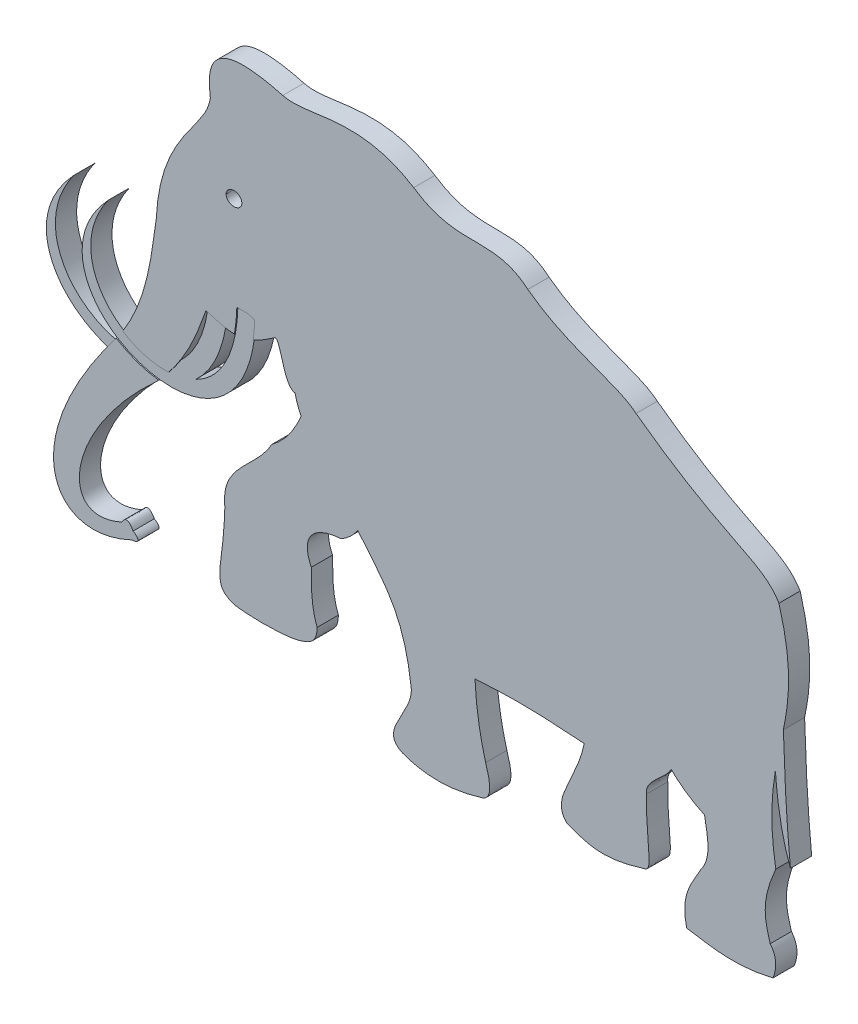
SolidWorks part; units mm, degrees
ref_plane "Plan de face" through (0, 0, 0) normal (0, 0, 1) x (1, 0, 0)
ref_plane "Plan de dessus" through (0, 0, 0) normal (0, 1, 0) x (1, 0, 0)
ref_plane "Plan de droite" through (0, 0, 0) normal (1, 0, 0) x (0, 0, -1)
sketch "Model" plane through (0, 0, 0) normal (0, 0, 1) x (1, 0, 0)
  line L0 (248.1084, -239.3251) -> (301.9242, -314.2399)
  line L1 (686.5238, -260.843) -> (694.4103, -257.2566)
  spline S0 degree 3 poles (301.9242, -314.2399) (295.2295, -323.0056) (293.23, -331.7727) (278.7279, -340.5398) knots 0 0 0 0 1 1 1 1
  spline S1 degree 3 poles (278.7279, -340.5398) (254.5292, -342.3381) (239.2631, -354.1813) (250.429, -377.9962) knots 1 1 1 1 2 2 2 2
  spline S2 degree 3 poles (250.429, -377.9962) (250.7714, -393.4048) (249.7741, -408.8129) (255.9949, -424.2201) knots 2 2 2 2 3 3 3 3
  spline S3 degree 3 poles (255.9949, -424.2201) (255.639, -432.7619) (253.4598, -438.1342) (245.3247, -440.9567) knots 3 3 3 3 4 4 4 4
  spline S4 degree 3 poles (245.3247, -440.9567) (232.7989, -448.2596) (189.6535, -447.0308) (178.5197, -444.941) knots 4 4 4 4 5 5 5 5
  spline S5 degree 3 poles (178.5197, -444.941) (161.3948, -439.7392) (164.8538, -429.6816) (164.602, -419.4387) knots 5 5 5 5 6 6 6 6
  spline S6 degree 3 poles (164.602, -419.4387) (166.1483, -404.8297) (169.703, -383.7044) (168.7761, -361.6592) knots 6 6 6 6 7 7 7 7
  spline S7 degree 3 poles (168.7761, -361.6592) (169.3183, -333.355) (200.344, -320.6405) (212.8499, -296.7061) knots 7 7 7 7 8 8 8 8
  spline S8 degree 3 poles (212.8499, -296.7061) (232.5185, -282.1109) (240.8466, -262.3516) (248.1084, -239.3251) knots 8 8 8 8 9 9 9 9
  spline S9 degree 3 poles (25.6291, -171.1053) (-78.331, -281.7881) (164.8394, -380.2969) (171.1134, -200.6289) knots 2 2 2 2 3 3 3 3
  spline S10 degree 3 poles (153.5278, -198.3402) (149.0453, -356.6449) (-50.4862, -276.4662) (25.6291, -171.1053) knots 1 1 1 1 2 2 2 2
  spline S11 degree 3 poles (171.1134, -200.6289) (165.7403, -197.3457) (159.5823, -198.1088) (153.5278, -198.3402) knots 0 0 0 0 1 1 1 1
  spline S12 degree 3 poles (694.4103, -257.2566) (695.4208, -304.563) (697.1437, -351.666) (701.8335, -397.9202) knots 0 0 0 0 1 1 1 1
  spline S13 degree 3 poles (701.8335, -397.9202) (687.3431, -360.1465) (685.441, -308.9069) (686.5238, -260.843) knots 1 1 1 1 2 2 2 2
  spline S14 degree 3 poles (682.8079, -468.9333) (688.369, -475.8083) (689.7625, -484.4731) (685.4324, -495.5966) knots 31 31 31 31 32 32 32 32
  spline S15 degree 3 poles (688.0569, -405.4295) (674.1573, -436.5487) (677.1662, -450.4028) (682.8079, -468.9333) knots 30 30 30 30 31 31 31 31
  spline S16 degree 3 poles (691.0004, -187.0392) (719.3676, -283.9641) (670.9806, -305.2568) (688.0569, -405.4295) knots 29 29 29 29 30 30 30 30
  spline S17 degree 3 poles (556.3877, -99.5257) (642.7673, -162.7708) (674.5552, -159.525) (691.0004, -187.0392) knots 28 28 28 28 29 29 29 29
  spline S18 degree 3 poles (454.4856, -49.2743) (493.3074, -78.3308) (537.7653, -83.4723) (556.3877, -99.5257) knots 27 27 27 27 28 28 28 28
  spline S19 degree 3 poles (346.8861, -19.9704) (389.7375, -49.2339) (421.2332, -21.029) (454.4856, -49.2743) knots 26 26 26 26 27 27 27 27
  spline S20 degree 3 poles (223.5405, -6.4456) (248.6374, -12.988) (294.1249, 13.0793) (346.8861, -19.9704) knots 25 25 25 25 26 26 26 26
  spline S21 degree 3 poles (155.3066, -42.512) (150.0494, -7.9268) (163.8615, 9.5951) (223.5405, -6.4456) knots 24 24 24 24 25 25 25 25
  spline S22 degree 3 poles (104.3556, -166.7051) (108.0056, -90.8591) (151.5201, -71.6657) (155.3066, -42.512) knots 23 23 23 23 24 24 24 24
  spline S23 degree 3 poles (64.429, -285.9688) (97.7651, -242.8014) (99.6894, -195.1846) (104.3556, -166.7051) knots 22 22 22 22 23 23 23 23
  spline S24 degree 3 poles (81.2583, -440.227) (11.0648, -474.2336) (-33.8922, -415.6463) (64.429, -285.9688) knots 21 21 21 21 22 22 22 22
  spline S25 degree 3 poles (82.536, -432.3929) (85.8168, -434.031) (91.6451, -439.7382) (81.2583, -440.227) knots 20 20 20 20 21 21 21 21
  spline S26 degree 3 poles (72.0705, -430.2411) (76.0632, -422.4504) (80.7158, -428.6315) (82.536, -432.3929) knots 19 19 19 19 20 20 20 20
  spline S27 degree 3 poles (105.1497, -298.7683) (14.8816, -380.7089) (13.2057, -457.0612) (72.0705, -430.2411) knots 18 18 18 18 19 19 19 19
  spline S28 degree 3 poles (151.2097, -218.1993) (141.3571, -245.6541) (131.9728, -269.5625) (105.1497, -298.7683) knots 17 17 17 17 18 18 18 18
  spline S29 degree 3 poles (215.6607, -208.1153) (182.5696, -231.755) (171.7983, -223.2184) (151.2097, -218.1993) knots 16 16 16 16 17 17 17 17
  spline S30 degree 3 poles (235.1243, -243.405) (223.5218, -242.3888) (221.7119, -203.7932) (215.6607, -208.1153) knots 15 15 15 15 16 16 16 16
  spline S31 degree 3 poles (302.2716, -335.5513) (284.6381, -313.5233) (242.1377, -277.4728) (235.1243, -243.405) knots 14 14 14 14 15 15 15 15
  spline S32 degree 3 poles (344.4077, -428.0965) (337.8376, -374.1108) (319.875, -358.4822) (302.2716, -335.5513) knots 13 13 13 13 14 14 14 14
  spline S33 degree 3 poles (336.3884, -486.5801) (312.2133, -475.3205) (347.7843, -450.1141) (344.4077, -428.0965) knots 12 12 12 12 13 13 13 13
  spline S34 degree 3 poles (411.0902, -485.6468) (383.7985, -494.1735) (358.7337, -495.0502) (336.3884, -486.5801) knots 11 11 11 11 12 12 12 12
  spline S35 degree 3 poles (414.6968, -455.1905) (416.9182, -462.6339) (423.6596, -482.1542) (411.0902, -485.6468) knots 10 10 10 10 11 11 11 11
  spline S36 degree 3 poles (404.6223, -391.9048) (405.8026, -415.5826) (409.0097, -434.3886) (414.6968, -455.1905) knots 9 9 9 9 10 10 10 10
  spline S37 degree 3 poles (507.5976, -393.2142) (474.8275, -391.2485) (454.1935, -388.7491) (404.6223, -391.9048) knots 8 8 8 8 9 9 9 9
  spline S38 degree 3 poles (491.2286, -466.2926) (475.3057, -451.0646) (500.5186, -427.7775) (507.5976, -393.2142) knots 7 7 7 7 8 8 8 8
  spline S39 degree 3 poles (563.9287, -467.0888) (526.7358, -478.7256) (512.5024, -474.8272) (491.2286, -466.2926) knots 6 6 6 6 7 7 7 7
  spline S40 degree 3 poles (566.2676, -405.0037) (565.0839, -441.931) (573.8871, -466.4112) (563.9287, -467.0888) knots 5 5 5 5 6 6 6 6
  spline S41 degree 3 poles (589.7814, -373.1996) (581.9955, -386.1446) (564.8589, -392.8883) (566.2676, -405.0037) knots 4 4 4 4 5 5 5 5
  spline S42 degree 3 poles (620.9092, -394.8197) (613.1905, -391.6305) (596.3109, -381.2932) (589.7814, -373.1996) knots 3 3 3 3 4 4 4 4
  spline S43 degree 3 poles (617.1985, -441.4959) (628.4719, -426.468) (623.235, -409.8472) (620.9092, -394.8197) knots 2 2 2 2 3 3 3 3
  spline S44 degree 3 poles (604.0768, -495.5966) (597.9194, -468.5168) (609.2765, -456.4831) (617.1985, -441.4959) knots 1 1 1 1 2 2 2 2
  spline S45 degree 3 poles (685.4324, -495.5966) (647.9339, -504.5132) (627.4122, -498.8457) (604.0768, -495.5966) knots 0 0 0 0 1 1 1 1
  spline S46 degree 3 poles (590.6978, -374.1904) (539.7869, -400.8334) (527.9161, -394.1892) (506.1403, -393.1667) knots 1 1 1 1 2 2 2 2
  spline S47 degree 3 poles (549.6633, -223.3853) (544.7302, -281.4936) (550.1197, -334.0427) (590.6978, -374.1904) knots 0 0 0 0 1 1 1 1
  spline S48 degree 3 poles (426.2572, -340.9377) (425.0145, -313.7827) (425.3804, -284.5528) (414.66, -269.6101) knots 1 1 1 1 2 2 2 2
  spline S49 degree 3 poles (404.9179, -391.9423) (405.9508, -371.4602) (421.8867, -360.439) (426.2572, -340.9377) knots 0 0 0 0 1 1 1 1
  spline S50 degree 3 poles (269.9127, -224.1827) (248.4308, -210.3968) (243.355, -183.4512) (227.2309, -166.801) knots 4 4 4 4 5 5 5 5
  spline S51 degree 3 poles (351.1024, -119.382) (294.0392, -147.0682) (290.6761, -187.727) (269.9127, -224.1827) knots 3 3 3 3 4 4 4 4
  spline S52 degree 3 poles (368.2673, -91.4885) (362.545, -102.9) (356.8227, -118.7907) (351.1024, -119.382) knots 2 2 2 2 3 3 3 3
  spline S53 degree 3 poles (334.864, -58.0152) (368.9673, -57.1161) (357.1369, -80.3288) (368.2673, -91.4885) knots 1 1 1 1 2 2 2 2
  spline S54 degree 3 poles (229.5515, -48.8509) (256.9822, -39.8213) (270.9943, -60.5377) (334.864, -58.0152) knots 0 0 0 0 1 1 1 1
  spline S55 degree 3 poles (185.0142, -113.6037) (185.0142, -109.9723) (181.6895, -107.029) (177.5912, -107.029) (173.4909, -107.029) (170.1679, -109.9723) (170.1679, -113.6037) knots 2 2 2 2 3 3 3 4 4 4 4
  spline S56 degree 3 poles (170.1679, -113.6037) (170.1679, -117.2352) (173.4909, -120.1785) (177.5912, -120.1785) (181.6895, -120.1785) (185.0142, -117.2352) (185.0142, -113.6037) knots 0 0 0 0 1 1 1 2 2 2 2
  spline S57 degree 3 poles (58.1685, -175.0475) (-41.0917, -280.725) (191.0848, -374.7819) (197.0769, -203.2358) knots 2 2 2 2 3 3 3 3
  spline S58 degree 3 poles (180.286, -201.0508) (176.0068, -352.1983) (-14.5056, -275.6445) (58.1685, -175.0475) knots 1 1 1 1 2 2 2 2
  spline S59 degree 3 poles (197.0769, -203.2358) (191.9463, -200.101) (186.0669, -200.8293) (180.286, -201.0508) knots 0 0 0 0 1 1 1 1
extrude "Boss.-Extru.1" add sketch "Model" along normal blind 20 contours S59 S57 S29 S30 S31 S8 L0 S0 S32 S33 S34 S35 S36 S37 S38 S46 S41 S42 S47 S43 S44 S45 S14 S15 S16 S13 L1 S12 S17 S18 S19 S20 S21 S22 S23 S58 S10 S28 | S0 S31 S8 S7 S6 S5 S4 S3 S2 S1 | S41 S46 S38 S39 S40 | S28 S9 S24 S25 S26 S27 | S57 S10 S23 S24 S9 S28 | S57 S23 S10 | S58 S28 S10 | S29 S9 S11 S10 | S13 L1 S12 | L0 S0 S1 S2 S3 S4 S5 S6 S7 S8 region at (415.0252, -224.2077, 0) region at (219.9742, -365.8319, 0) region at (161.7862, -209.6887, 0) region at (44.5341, -370.9669, 0) region at (77.4933, -294.0595, 0) region at (114.7872, -281.6253, 0) region at (68.3589, -285.0647, 0) region at (531.9975, -433.1095, 0)
sketch "Esquisse3" plane through (0, 0, 0) normal (0, 0, 1) x (1, 0, 0)
  line L0 (248.1084, -239.3251) -> (301.9242, -314.2399)
  line L1 (686.5238, -260.843) -> (694.4103, -257.2566)
  spline S0 degree 3 poles (301.9242, -314.2399) (295.2295, -323.0056) (293.23, -331.7727) (278.7279, -340.5398) knots 0 0 0 0 1 1 1 1
  spline S1 degree 3 poles (278.7279, -340.5398) (254.5292, -342.3381) (239.2631, -354.1813) (250.429, -377.9962) knots 1 1 1 1 2 2 2 2
  spline S2 degree 3 poles (250.429, -377.9962) (250.7714, -393.4048) (249.7741, -408.8129) (255.9949, -424.2201) knots 2 2 2 2 3 3 3 3
  spline S3 degree 3 poles (255.9949, -424.2201) (255.639, -432.7619) (253.4598, -438.1342) (245.3247, -440.9567) knots 3 3 3 3 4 4 4 4
  spline S4 degree 3 poles (245.3247, -440.9567) (232.7989, -448.2596) (189.6535, -447.0308) (178.5197, -444.941) knots 4 4 4 4 5 5 5 5
  spline S5 degree 3 poles (178.5197, -444.941) (161.3948, -439.7392) (164.8538, -429.6816) (164.602, -419.4387) knots 5 5 5 5 6 6 6 6
  spline S6 degree 3 poles (164.602, -419.4387) (166.1483, -404.8297) (169.703, -383.7044) (168.7761, -361.6592) knots 6 6 6 6 7 7 7 7
  spline S7 degree 3 poles (168.7761, -361.6592) (169.3183, -333.355) (200.344, -320.6405) (212.8499, -296.7061) knots 7 7 7 7 8 8 8 8
  spline S8 degree 3 poles (212.8499, -296.7061) (232.5185, -282.1109) (240.8466, -262.3516) (248.1084, -239.3251) knots 8 8 8 8 9 9 9 9
  spline S9 degree 3 poles (25.6291, -171.1053) (-78.331, -281.7881) (164.8394, -380.2969) (171.1134, -200.6289) knots 2 2 2 2 3 3 3 3
  spline S10 degree 3 poles (153.5278, -198.3402) (149.0453, -356.6449) (-50.4862, -276.4662) (25.6291, -171.1053) knots 1 1 1 1 2 2 2 2
  spline S11 degree 3 poles (171.1134, -200.6289) (165.7403, -197.3457) (159.5823, -198.1088) (153.5278, -198.3402) knots 0 0 0 0 1 1 1 1
  spline S12 degree 3 poles (694.4103, -257.2566) (695.4208, -304.563) (697.1437, -351.666) (701.8335, -397.9202) knots 0 0 0 0 1 1 1 1
  spline S13 degree 3 poles (701.8335, -397.9202) (687.3431, -360.1465) (685.441, -308.9069) (686.5238, -260.843) knots 1 1 1 1 2 2 2 2
  spline S14 degree 3 poles (682.8079, -468.9333) (688.369, -475.8083) (689.7625, -484.4731) (685.4324, -495.5966) knots 31 31 31 31 32 32 32 32
  spline S15 degree 3 poles (688.0569, -405.4295) (674.1573, -436.5487) (677.1662, -450.4028) (682.8079, -468.9333) knots 30 30 30 30 31 31 31 31
  spline S16 degree 3 poles (691.0004, -187.0392) (719.3676, -283.9641) (670.9806, -305.2568) (688.0569, -405.4295) knots 29 29 29 29 30 30 30 30
  spline S17 degree 3 poles (556.3877, -99.5257) (642.7673, -162.7708) (674.5552, -159.525) (691.0004, -187.0392) knots 28 28 28 28 29 29 29 29
  spline S18 degree 3 poles (454.4856, -49.2743) (493.3074, -78.3308) (537.7653, -83.4723) (556.3877, -99.5257) knots 27 27 27 27 28 28 28 28
  spline S19 degree 3 poles (346.8861, -19.9704) (389.7375, -49.2339) (421.2332, -21.029) (454.4856, -49.2743) knots 26 26 26 26 27 27 27 27
  spline S20 degree 3 poles (223.5405, -6.4456) (248.6374, -12.988) (294.1249, 13.0793) (346.8861, -19.9704) knots 25 25 25 25 26 26 26 26
  spline S21 degree 3 poles (155.3066, -42.512) (150.0494, -7.9268) (163.8615, 9.5951) (223.5405, -6.4456) knots 24 24 24 24 25 25 25 25
  spline S22 degree 3 poles (104.3556, -166.7051) (108.0056, -90.8591) (151.5201, -71.6657) (155.3066, -42.512) knots 23 23 23 23 24 24 24 24
  spline S23 degree 3 poles (64.429, -285.9688) (97.7651, -242.8014) (99.6894, -195.1846) (104.3556, -166.7051) knots 22 22 22 22 23 23 23 23
  spline S24 degree 3 poles (81.2583, -440.227) (11.0648, -474.2336) (-33.8922, -415.6463) (64.429, -285.9688) knots 21 21 21 21 22 22 22 22
  spline S25 degree 3 poles (82.536, -432.3929) (85.8168, -434.031) (91.6451, -439.7382) (81.2583, -440.227) knots 20 20 20 20 21 21 21 21
  spline S26 degree 3 poles (72.0705, -430.2411) (76.0632, -422.4504) (80.7158, -428.6315) (82.536, -432.3929) knots 19 19 19 19 20 20 20 20
  spline S27 degree 3 poles (105.1497, -298.7683) (14.8816, -380.7089) (13.2057, -457.0612) (72.0705, -430.2411) knots 18 18 18 18 19 19 19 19
  spline S28 degree 3 poles (151.2097, -218.1993) (141.3571, -245.6541) (131.9728, -269.5625) (105.1497, -298.7683) knots 17 17 17 17 18 18 18 18
  spline S29 degree 3 poles (215.6607, -208.1153) (182.5696, -231.755) (171.7983, -223.2184) (151.2097, -218.1993) knots 16 16 16 16 17 17 17 17
  spline S30 degree 3 poles (235.1243, -243.405) (223.5218, -242.3888) (221.7119, -203.7932) (215.6607, -208.1153) knots 15 15 15 15 16 16 16 16
  spline S31 degree 3 poles (302.2716, -335.5513) (284.6381, -313.5233) (242.1377, -277.4728) (235.1243, -243.405) knots 14 14 14 14 15 15 15 15
  spline S32 degree 3 poles (344.4077, -428.0965) (337.8376, -374.1108) (319.875, -358.4822) (302.2716, -335.5513) knots 13 13 13 13 14 14 14 14
  spline S33 degree 3 poles (336.3884, -486.5801) (312.2133, -475.3205) (347.7843, -450.1141) (344.4077, -428.0965) knots 12 12 12 12 13 13 13 13
  spline S34 degree 3 poles (411.0902, -485.6468) (383.7985, -494.1735) (358.7337, -495.0502) (336.3884, -486.5801) knots 11 11 11 11 12 12 12 12
  spline S35 degree 3 poles (414.6968, -455.1905) (416.9182, -462.6339) (423.6596, -482.1542) (411.0902, -485.6468) knots 10 10 10 10 11 11 11 11
  spline S36 degree 3 poles (404.6223, -391.9048) (405.8026, -415.5826) (409.0097, -434.3886) (414.6968, -455.1905) knots 9 9 9 9 10 10 10 10
  spline S37 degree 3 poles (507.5976, -393.2142) (474.8275, -391.2485) (454.1935, -388.7491) (404.6223, -391.9048) knots 8 8 8 8 9 9 9 9
  spline S38 degree 3 poles (491.2286, -466.2926) (475.3057, -451.0646) (500.5186, -427.7775) (507.5976, -393.2142) knots 7 7 7 7 8 8 8 8
  spline S39 degree 3 poles (563.9287, -467.0888) (526.7358, -478.7256) (512.5024, -474.8272) (491.2286, -466.2926) knots 6 6 6 6 7 7 7 7
  spline S40 degree 3 poles (566.2676, -405.0037) (565.0839, -441.931) (573.8871, -466.4112) (563.9287, -467.0888) knots 5 5 5 5 6 6 6 6
  spline S41 degree 3 poles (589.7814, -373.1996) (581.9955, -386.1446) (564.8589, -392.8883) (566.2676, -405.0037) knots 4 4 4 4 5 5 5 5
  spline S42 degree 3 poles (620.9092, -394.8197) (613.1905, -391.6305) (596.3109, -381.2932) (589.7814, -373.1996) knots 3 3 3 3 4 4 4 4
  spline S43 degree 3 poles (617.1985, -441.4959) (628.4719, -426.468) (623.235, -409.8472) (620.9092, -394.8197) knots 2 2 2 2 3 3 3 3
  spline S44 degree 3 poles (604.0768, -495.5966) (597.9194, -468.5168) (609.2765, -456.4831) (617.1985, -441.4959) knots 1 1 1 1 2 2 2 2
  spline S45 degree 3 poles (685.4324, -495.5966) (647.9339, -504.5132) (627.4122, -498.8457) (604.0768, -495.5966) knots 0 0 0 0 1 1 1 1
  spline S46 degree 3 poles (590.6978, -374.1904) (539.7869, -400.8334) (527.9161, -394.1892) (506.1403, -393.1667) knots 1 1 1 1 2 2 2 2
  spline S47 degree 3 poles (549.6633, -223.3853) (544.7302, -281.4936) (550.1197, -334.0427) (590.6978, -374.1904) knots 0 0 0 0 1 1 1 1
  spline S48 degree 3 poles (426.2572, -340.9377) (425.0145, -313.7827) (425.3804, -284.5528) (414.66, -269.6101) knots 1 1 1 1 2 2 2 2
  spline S49 degree 3 poles (404.9179, -391.9423) (405.9508, -371.4602) (421.8867, -360.439) (426.2572, -340.9377) knots 0 0 0 0 1 1 1 1
  spline S50 degree 3 poles (269.9127, -224.1827) (248.4308, -210.3968) (243.355, -183.4512) (227.2309, -166.801) knots 4 4 4 4 5 5 5 5
  spline S51 degree 3 poles (351.1024, -119.382) (294.0392, -147.0682) (290.6761, -187.727) (269.9127, -224.1827) knots 3 3 3 3 4 4 4 4
  spline S52 degree 3 poles (368.2673, -91.4885) (362.545, -102.9) (356.8227, -118.7907) (351.1024, -119.382) knots 2 2 2 2 3 3 3 3
  spline S53 degree 3 poles (334.864, -58.0152) (368.9673, -57.1161) (357.1369, -80.3288) (368.2673, -91.4885) knots 1 1 1 1 2 2 2 2
  spline S54 degree 3 poles (229.5515, -48.8509) (256.9822, -39.8213) (270.9943, -60.5377) (334.864, -58.0152) knots 0 0 0 0 1 1 1 1
  spline S55 degree 3 poles (185.0142, -113.6037) (185.0142, -109.9723) (181.6895, -107.029) (177.5912, -107.029) (173.4909, -107.029) (170.1679, -109.9723) (170.1679, -113.6037) knots 2 2 2 2 3 3 3 4 4 4 4
  spline S56 degree 3 poles (170.1679, -113.6037) (170.1679, -117.2352) (173.4909, -120.1785) (177.5912, -120.1785) (181.6895, -120.1785) (185.0142, -117.2352) (185.0142, -113.6037) knots 0 0 0 0 1 1 1 2 2 2 2
  spline S57 degree 3 poles (58.1685, -175.0475) (-41.0917, -280.725) (191.0848, -374.7819) (197.0769, -203.2358) knots 2 2 2 2 3 3 3 3
  spline S58 degree 3 poles (180.286, -201.0508) (176.0068, -352.1983) (-14.5056, -275.6445) (58.1685, -175.0475) knots 1 1 1 1 2 2 2 2
  spline S59 degree 3 poles (197.0769, -203.2358) (191.9463, -200.101) (186.0669, -200.8293) (180.286, -201.0508) knots 0 0 0 0 1 1 1 1
extrude "Boss.-Extru.2" add sketch "Esquisse3" along normal blind 19 contours S29 S58 S9 S57 | S58 S9 S29 S10 S28 | S57 S59 S58 S29 | S28 S58 S10 S57 | S9 S58 S28 S57 | S58 S57 S59 | S9 S11 S10 region at (165.0031, -263.0982, 0) region at (187.5826, -211.9729, 0) region at (121.2048, -289.3126, 0) region at (147.2657, -253.5134, 0) region at (98.2499, -290.4263, 0)
sketch "Esquisse6" plane through (0, 0, 0) normal (0, 0, 1) x (1, 0, 0)
  line L0 (248.1084, -239.3251) -> (301.9242, -314.2399)
  line L1 (686.5238, -260.843) -> (694.4103, -257.2566)
  spline S0 degree 3 poles (301.9242, -314.2399) (295.2295, -323.0056) (293.23, -331.7727) (278.7279, -340.5398) knots 0 0 0 0 1 1 1 1
  spline S1 degree 3 poles (278.7279, -340.5398) (254.5292, -342.3381) (239.2631, -354.1813) (250.429, -377.9962) knots 1 1 1 1 2 2 2 2
  spline S2 degree 3 poles (250.429, -377.9962) (250.7714, -393.4048) (249.7741, -408.8129) (255.9949, -424.2201) knots 2 2 2 2 3 3 3 3
  spline S3 degree 3 poles (255.9949, -424.2201) (255.639, -432.7619) (253.4598, -438.1342) (245.3247, -440.9567) knots 3 3 3 3 4 4 4 4
  spline S4 degree 3 poles (245.3247, -440.9567) (232.7989, -448.2596) (189.6535, -447.0308) (178.5197, -444.941) knots 4 4 4 4 5 5 5 5
  spline S5 degree 3 poles (178.5197, -444.941) (161.3948, -439.7392) (164.8538, -429.6816) (164.602, -419.4387) knots 5 5 5 5 6 6 6 6
  spline S6 degree 3 poles (164.602, -419.4387) (166.1483, -404.8297) (169.703, -383.7044) (168.7761, -361.6592) knots 6 6 6 6 7 7 7 7
  spline S7 degree 3 poles (168.7761, -361.6592) (169.3183, -333.355) (200.344, -320.6405) (212.8499, -296.7061) knots 7 7 7 7 8 8 8 8
  spline S8 degree 3 poles (212.8499, -296.7061) (232.5185, -282.1109) (240.8466, -262.3516) (248.1084, -239.3251) knots 8 8 8 8 9 9 9 9
  spline S9 degree 3 poles (25.6291, -171.1053) (-78.331, -281.7881) (164.8394, -380.2969) (171.1134, -200.6289) knots 2 2 2 2 3 3 3 3
  spline S10 degree 3 poles (153.5278, -198.3402) (149.0453, -356.6449) (-50.4862, -276.4662) (25.6291, -171.1053) knots 1 1 1 1 2 2 2 2
  spline S11 degree 3 poles (171.1134, -200.6289) (165.7403, -197.3457) (159.5823, -198.1088) (153.5278, -198.3402) knots 0 0 0 0 1 1 1 1
  spline S12 degree 3 poles (694.4103, -257.2566) (695.4208, -304.563) (697.1437, -351.666) (701.8335, -397.9202) knots 0 0 0 0 1 1 1 1
  spline S13 degree 3 poles (701.8335, -397.9202) (687.3431, -360.1465) (685.441, -308.9069) (686.5238, -260.843) knots 1 1 1 1 2 2 2 2
  spline S14 degree 3 poles (682.8079, -468.9333) (688.369, -475.8083) (689.7625, -484.4731) (685.4324, -495.5966) knots 31 31 31 31 32 32 32 32
  spline S15 degree 3 poles (688.0569, -405.4295) (674.1573, -436.5487) (677.1662, -450.4028) (682.8079, -468.9333) knots 30 30 30 30 31 31 31 31
  spline S16 degree 3 poles (691.0004, -187.0392) (719.3676, -283.9641) (670.9806, -305.2568) (688.0569, -405.4295) knots 29 29 29 29 30 30 30 30
  spline S17 degree 3 poles (556.3877, -99.5257) (642.7673, -162.7708) (674.5552, -159.525) (691.0004, -187.0392) knots 28 28 28 28 29 29 29 29
  spline S18 degree 3 poles (454.4856, -49.2743) (493.3074, -78.3308) (537.7653, -83.4723) (556.3877, -99.5257) knots 27 27 27 27 28 28 28 28
  spline S19 degree 3 poles (346.8861, -19.9704) (389.7375, -49.2339) (421.2332, -21.029) (454.4856, -49.2743) knots 26 26 26 26 27 27 27 27
  spline S20 degree 3 poles (223.5405, -6.4456) (248.6374, -12.988) (294.1249, 13.0793) (346.8861, -19.9704) knots 25 25 25 25 26 26 26 26
  spline S21 degree 3 poles (155.3066, -42.512) (150.0494, -7.9268) (163.8615, 9.5951) (223.5405, -6.4456) knots 24 24 24 24 25 25 25 25
  spline S22 degree 3 poles (104.3556, -166.7051) (108.0056, -90.8591) (151.5201, -71.6657) (155.3066, -42.512) knots 23 23 23 23 24 24 24 24
  spline S23 degree 3 poles (64.429, -285.9688) (97.7651, -242.8014) (99.6894, -195.1846) (104.3556, -166.7051) knots 22 22 22 22 23 23 23 23
  spline S24 degree 3 poles (81.2583, -440.227) (11.0648, -474.2336) (-33.8922, -415.6463) (64.429, -285.9688) knots 21 21 21 21 22 22 22 22
  spline S25 degree 3 poles (82.536, -432.3929) (85.8168, -434.031) (91.6451, -439.7382) (81.2583, -440.227) knots 20 20 20 20 21 21 21 21
  spline S26 degree 3 poles (72.0705, -430.2411) (76.0632, -422.4504) (80.7158, -428.6315) (82.536, -432.3929) knots 19 19 19 19 20 20 20 20
  spline S27 degree 3 poles (105.1497, -298.7683) (14.8816, -380.7089) (13.2057, -457.0612) (72.0705, -430.2411) knots 18 18 18 18 19 19 19 19
  spline S28 degree 3 poles (151.2097, -218.1993) (141.3571, -245.6541) (131.9728, -269.5625) (105.1497, -298.7683) knots 17 17 17 17 18 18 18 18
  spline S29 degree 3 poles (215.6607, -208.1153) (182.5696, -231.755) (171.7983, -223.2184) (151.2097, -218.1993) knots 16 16 16 16 17 17 17 17
  spline S30 degree 3 poles (235.1243, -243.405) (223.5218, -242.3888) (221.7119, -203.7932) (215.6607, -208.1153) knots 15 15 15 15 16 16 16 16
  spline S31 degree 3 poles (302.2716, -335.5513) (284.6381, -313.5233) (242.1377, -277.4728) (235.1243, -243.405) knots 14 14 14 14 15 15 15 15
  spline S32 degree 3 poles (344.4077, -428.0965) (337.8376, -374.1108) (319.875, -358.4822) (302.2716, -335.5513) knots 13 13 13 13 14 14 14 14
  spline S33 degree 3 poles (336.3884, -486.5801) (312.2133, -475.3205) (347.7843, -450.1141) (344.4077, -428.0965) knots 12 12 12 12 13 13 13 13
  spline S34 degree 3 poles (411.0902, -485.6468) (383.7985, -494.1735) (358.7337, -495.0502) (336.3884, -486.5801) knots 11 11 11 11 12 12 12 12
  spline S35 degree 3 poles (414.6968, -455.1905) (416.9182, -462.6339) (423.6596, -482.1542) (411.0902, -485.6468) knots 10 10 10 10 11 11 11 11
  spline S36 degree 3 poles (404.6223, -391.9048) (405.8026, -415.5826) (409.0097, -434.3886) (414.6968, -455.1905) knots 9 9 9 9 10 10 10 10
  spline S37 degree 3 poles (507.5976, -393.2142) (474.8275, -391.2485) (454.1935, -388.7491) (404.6223, -391.9048) knots 8 8 8 8 9 9 9 9
  spline S38 degree 3 poles (491.2286, -466.2926) (475.3057, -451.0646) (500.5186, -427.7775) (507.5976, -393.2142) knots 7 7 7 7 8 8 8 8
  spline S39 degree 3 poles (563.9287, -467.0888) (526.7358, -478.7256) (512.5024, -474.8272) (491.2286, -466.2926) knots 6 6 6 6 7 7 7 7
  spline S40 degree 3 poles (566.2676, -405.0037) (565.0839, -441.931) (573.8871, -466.4112) (563.9287, -467.0888) knots 5 5 5 5 6 6 6 6
  spline S41 degree 3 poles (589.7814, -373.1996) (581.9955, -386.1446) (564.8589, -392.8883) (566.2676, -405.0037) knots 4 4 4 4 5 5 5 5
  spline S42 degree 3 poles (620.9092, -394.8197) (613.1905, -391.6305) (596.3109, -381.2932) (589.7814, -373.1996) knots 3 3 3 3 4 4 4 4
  spline S43 degree 3 poles (617.1985, -441.4959) (628.4719, -426.468) (623.235, -409.8472) (620.9092, -394.8197) knots 2 2 2 2 3 3 3 3
  spline S44 degree 3 poles (604.0768, -495.5966) (597.9194, -468.5168) (609.2765, -456.4831) (617.1985, -441.4959) knots 1 1 1 1 2 2 2 2
  spline S45 degree 3 poles (685.4324, -495.5966) (647.9339, -504.5132) (627.4122, -498.8457) (604.0768, -495.5966) knots 0 0 0 0 1 1 1 1
  spline S46 degree 3 poles (590.6978, -374.1904) (539.7869, -400.8334) (527.9161, -394.1892) (506.1403, -393.1667) knots 1 1 1 1 2 2 2 2
  spline S47 degree 3 poles (549.6633, -223.3853) (544.7302, -281.4936) (550.1197, -334.0427) (590.6978, -374.1904) knots 0 0 0 0 1 1 1 1
  spline S48 degree 3 poles (426.2572, -340.9377) (425.0145, -313.7827) (425.3804, -284.5528) (414.66, -269.6101) knots 1 1 1 1 2 2 2 2
  spline S49 degree 3 poles (404.9179, -391.9423) (405.9508, -371.4602) (421.8867, -360.439) (426.2572, -340.9377) knots 0 0 0 0 1 1 1 1
  spline S50 degree 3 poles (269.9127, -224.1827) (248.4308, -210.3968) (243.355, -183.4512) (227.2309, -166.801) knots 4 4 4 4 5 5 5 5
  spline S51 degree 3 poles (351.1024, -119.382) (294.0392, -147.0682) (290.6761, -187.727) (269.9127, -224.1827) knots 3 3 3 3 4 4 4 4
  spline S52 degree 3 poles (368.2673, -91.4885) (362.545, -102.9) (356.8227, -118.7907) (351.1024, -119.382) knots 2 2 2 2 3 3 3 3
  spline S53 degree 3 poles (334.864, -58.0152) (368.9673, -57.1161) (357.1369, -80.3288) (368.2673, -91.4885) knots 1 1 1 1 2 2 2 2
  spline S54 degree 3 poles (229.5515, -48.8509) (256.9822, -39.8213) (270.9943, -60.5377) (334.864, -58.0152) knots 0 0 0 0 1 1 1 1
  spline S55 degree 3 poles (185.0142, -113.6037) (185.0142, -109.9723) (181.6895, -107.029) (177.5912, -107.029) (173.4909, -107.029) (170.1679, -109.9723) (170.1679, -113.6037) knots 2 2 2 2 3 3 3 4 4 4 4
  spline S56 degree 3 poles (170.1679, -113.6037) (170.1679, -117.2352) (173.4909, -120.1785) (177.5912, -120.1785) (181.6895, -120.1785) (185.0142, -117.2352) (185.0142, -113.6037) knots 0 0 0 0 1 1 1 2 2 2 2
  spline S57 degree 3 poles (58.1685, -175.0475) (-41.0917, -280.725) (191.0848, -374.7819) (197.0769, -203.2358) knots 2 2 2 2 3 3 3 3
  spline S58 degree 3 poles (180.286, -201.0508) (176.0068, -352.1983) (-14.5056, -275.6445) (58.1685, -175.0475) knots 1 1 1 1 2 2 2 2
  spline S59 degree 3 poles (197.0769, -203.2358) (191.9463, -200.101) (186.0669, -200.8293) (180.286, -201.0508) knots 0 0 0 0 1 1 1 1
extrude "Boss.-Extru.3" add sketch "Esquisse6" against normal blind 1 contours S9 S24 S23 S10 | S58 S9 S29 S10 S28 | S29 S9 S11 S10 | S23 S58 S57 | S29 S58 S9 S57 | S10 S9 S11 region at (165.0031, -263.0982, 0) region at (161.7862, -209.6887, 0) region at (147.2657, -253.5134, 0) region at (3.4102, -242.5825, 0) region at (34.7621, -231.5394, 0)
